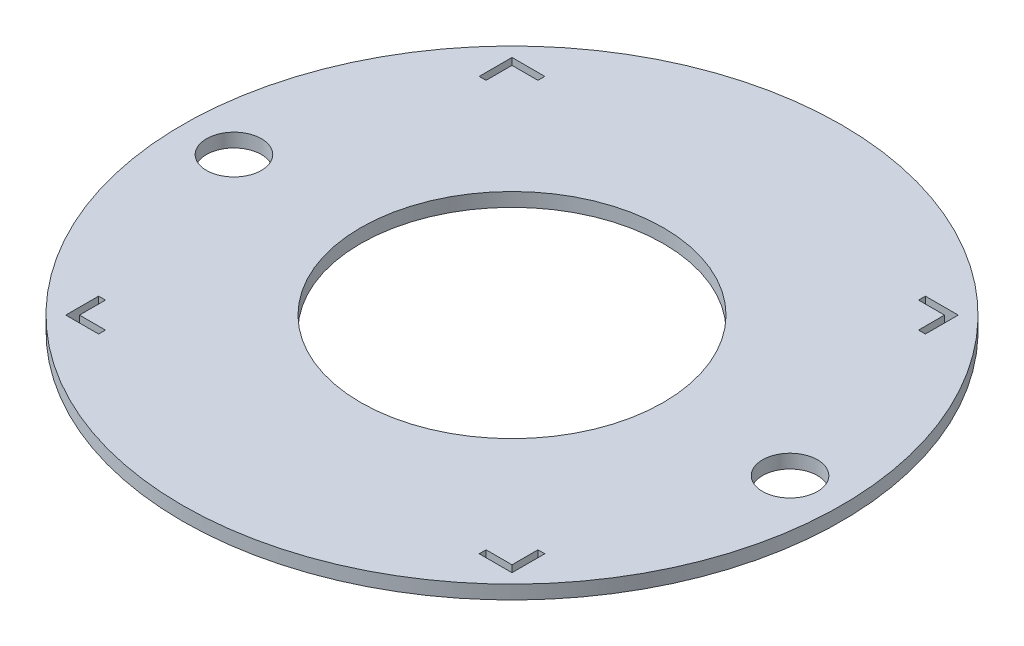
SolidWorks part; units mm, degrees
material "PE Low/Medium Density"
ref_plane "Front Plane" through (0, 0, 0) normal (0, 0, 1) x (1, 0, 0)
ref_plane "Top Plane" through (0, 0, 0) normal (0, 1, 0) x (1, 0, 0)
ref_plane "Right Plane" through (0, 0, 0) normal (1, 0, 0) x (0, 0, -1)
sketch "Sketch1" plane through (0, 0, 0) normal (0, 1, 0) x (1, 0, 0)
  line L0 (-50, 50) -> (-50, 44)
  line L1 (-50, -50) -> (50, -50) construction
  line L2 (-50, -50) -> (-50, 50) construction
  line L3 (-50, 50) -> (50, 50) construction
  line L4 (50, -50) -> (50, 50) construction
  line L5 (-50, -50) -> (50, 50) construction
  line L6 (-50, 50) -> (50, -50) construction
  line L7 (-50, 50) -> (-44, 50)
  line L8 (-51.5875, 51.5875) -> (-51.5875, 44)
  line L9 (-51.5875, 51.5875) -> (-44, 51.5875)
  line L10 (-51.5875, 44) -> (-50, 44)
  line L11 (-44, 51.5875) -> (-44, 50)
  line L12 (-50, 50) -> (-51.5875, 51.5875) construction
  line L13 (0, 0) -> (-50, 0) construction
  line L14 (51.5875, -44) -> (50, -44)
  line L15 (50, -50) -> (50, -44)
  line L16 (51.5875, -51.5875) -> (51.5875, -44)
  line L17 (51.5875, -51.5875) -> (44, -51.5875)
  line L18 (44, -51.5875) -> (44, -50)
  line L19 (50, -50) -> (44, -50)
  line L20 (-50, -50) -> (-44, -50)
  line L21 (-44, -51.5875) -> (-44, -50)
  line L22 (-51.5875, -51.5875) -> (-44, -51.5875)
  line L23 (-51.5875, -51.5875) -> (-51.5875, -44)
  line L24 (-51.5875, -44) -> (-50, -44)
  line L25 (-50, -50) -> (-50, -44)
  line L26 (51.5875, 51.5875) -> (44, 51.5875)
  line L27 (44, 51.5875) -> (44, 50)
  line L28 (50, 50) -> (44, 50)
  line L29 (50, 50) -> (50, 44)
  line L30 (51.5875, 51.5875) -> (51.5875, 44)
  line L31 (51.5875, 44) -> (50, 44)
  circle A0 centre (0, 0) radius 76.2
  dimension "D1" = 152.4
  dimension "D2" = 100
  dimension "D3" = 100
  dimension "D4" = 1.5875
  dimension "D5" = 1.5875
  dimension "D6" = 1.5875
extrude "Boss-Extrude1" add sketch "Sketch1" along normal blind 3.175
sketch "Sketch2" plane through (0, 3.175, 0) normal (0, 1, 0) x (1, 0, 0)
  circle A0 centre (0, 0) radius 35
  dimension "D1" = 70
extrude "Cut-Extrude1" cut sketch "Sketch2" against normal blind 3.175
sketch "Sketch3" plane through (0, 3.175, 0) normal (0, 1, 0) x (1, 0, 0)
  line L0 (-76.2, 0) -> (76.2, 0) construction
  line L1 (-51.5875, 51.5875) -> (51.5875, 51.5875) construction
  line L2 (-51.5875, 51.5875) -> (-51.5875, -51.5875) construction
  line L3 (-51.5875, -51.5875) -> (51.5875, -51.5875) construction
  line L4 (51.5875, 51.5875) -> (51.5875, -51.5875) construction
  circle A0 centre (0, 0) radius 76.2 construction
  circle A1 centre (-64.2875, 0) radius 6.35
  circle A2 centre (64.2875, 0) radius 6.35
  dimension "D1" = 12.7
  dimension "D2" = 12.7
  dimension "D3" = 12.7
  dimension "D4" = 12.7
extrude "Cut-Extrude2" cut sketch "Sketch3" against normal blind 10
